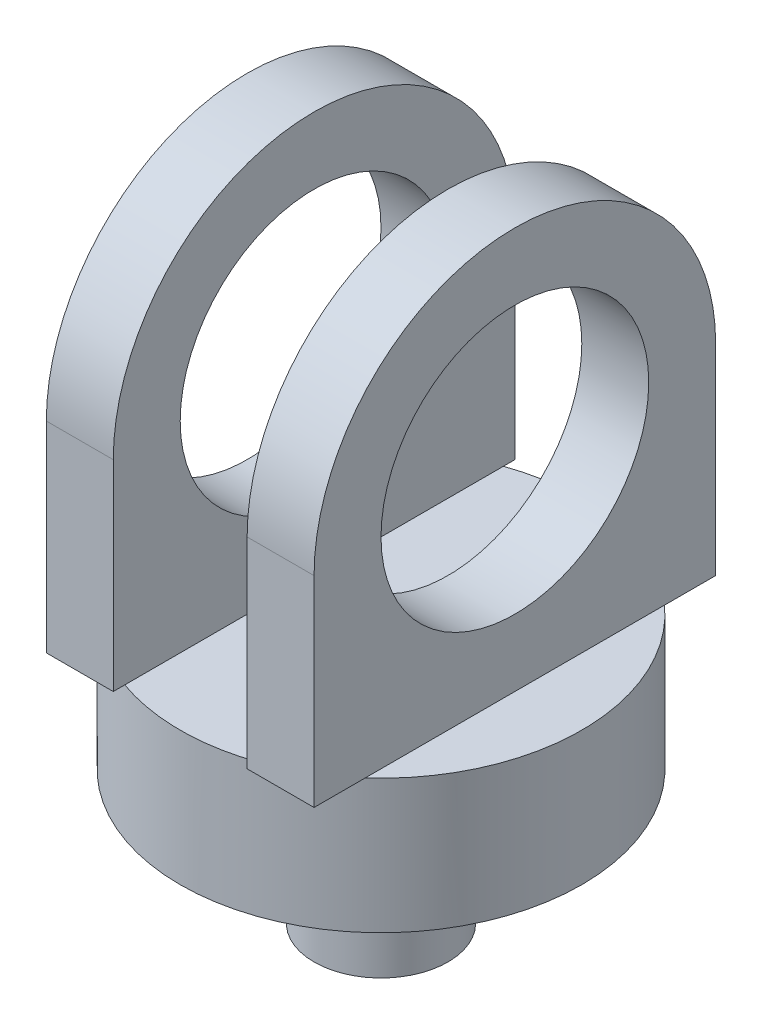
SolidWorks part; units mm, degrees
ref_plane "Front Plane" through (0, 0, 0) normal (0, 0, 1) x (1, 0, 0)
ref_plane "Top Plane" through (0, 0, 0) normal (0, 1, 0) x (1, 0, 0)
ref_plane "Right Plane" through (0, 0, 0) normal (1, 0, 0) x (0, 0, -1)
sketch "Sketch1" plane through (0, 0, 0) normal (0, 1, 0) x (1, 0, 0)
  circle A0 centre (0, 0) radius 6.35
  dimension "D1" = 12.7
extrude "ToFitIntoBearing" add sketch "Sketch1" along normal blind 12.7
sketch "Sketch2" plane through (0, 12.7, 0) normal (0, 1, 0) x (1, 0, 0)
  circle A0 centre (0, 0) radius 19.05
  dimension "D1" = 38.1
extrude "ToSitAtopBearing" add sketch "Sketch2" along normal blind 12.7
sketch "Sketch7" plane through (0, 0, 0) normal (1, 0, 0) x (0, 0, -1)
  line L0 (-19.05, 44.45) -> (-19.05, 25.4)
  line L1 (-19.05, 25.4) -> (19.05, 25.4)
  line L2 (19.05, 25.4) -> (-19.05, 25.4) construction
  line L3 (19.05, 25.4) -> (19.05, 44.45)
  line L4 (19.05, 12.7) -> (19.05, 25.4) construction
  circle A0 centre (0, 44.45) radius 12.7 construction
  arc A1 (-19.05, 44.45) -> (19.05, 44.45) centre (0, 44.45) cw
  point P4 (0, 44.4084)
  point P10 (21.1151, 44.4292)
  dimension "D1" = 25.4
  dimension "D2" = 19.05
extrude "Boss-Extrude3" add sketch "Sketch7" along normal blind 6.35 from offset 6.35 contours A1 L3 L1 L0
sketch "Sketch8" plane through (6.35, 0, 0) normal (-1, 0, 0) x (0, 0, 1)
  circle A0 centre (0, 44.45) radius 12.7
  dimension "D1" = 25.4
extrude "Cut-Extrude3" cut sketch "Sketch8" against normal blind 6.35
mirror "Mirror2" about plane through (0, 0, 0) normal (1, 0, 0) of "Cut-Extrude3", "Boss-Extrude3"
ref_axis "Axis1" through (12.7, 44.45, 0) along (-1, 0, 0)
ref_axis "Axis2" through (0, 12.7, 0) along (0, -1, 0)
